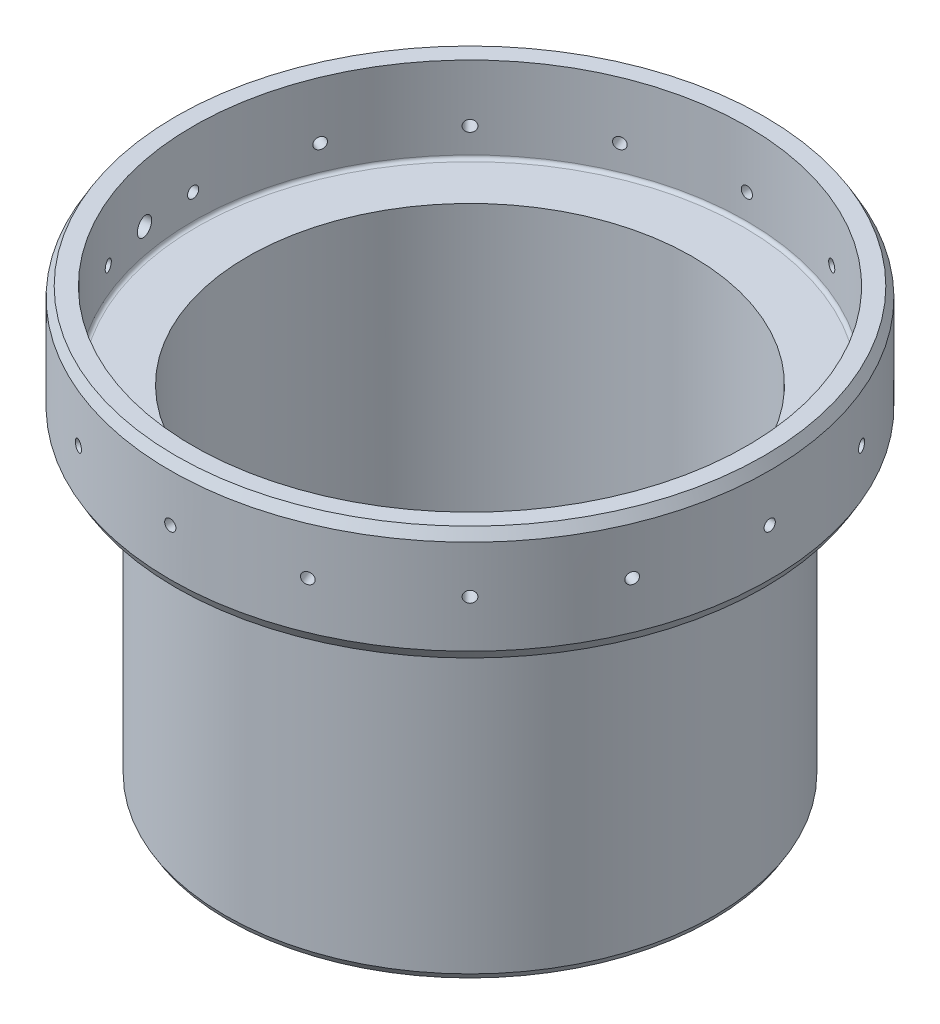
SolidWorks part; units mm, degrees
material "6061-T6 (SS)"
ref_plane "Front Plane" through (0, 0, 0) normal (0, 0, 1) x (1, 0, 0)
ref_plane "Top Plane" through (0, 0, 0) normal (0, 1, 0) x (1, 0, 0)
ref_plane "Right Plane" through (0, 0, 0) normal (1, 0, 0) x (0, 0, -1)
sketch "Sketch1" plane through (0, 0, 0) normal (0, 0, 1) x (1, 0, 0)
  line L0 (0, 0) -> (0, 9.1321) construction
  line L1 (0, 0) -> (-61.595, 0) construction
  line L2 (-61.595, 0) -> (-66.675, 0)
  line L3 (-66.675, 0) -> (-66.675, -25.4)
  line L4 (-66.675, -25.4) -> (-54.5465, -25.4)
  line L5 (-54.5465, -25.4) -> (-54.5465, -95.25)
  line L6 (-54.5465, -95.25) -> (-49.4665, -95.25)
  line L7 (-49.4665, -95.25) -> (-49.4665, -19.05)
  line L8 (-49.4665, -19.05) -> (-61.595, -19.05)
  line L9 (-61.595, -19.05) -> (-61.595, 0)
  dimension "D1" = 5.08
  dimension "D2" = 66.675
  dimension "D3" = 25.4
  dimension "D4" = 6.35
  dimension "D5" = 69.85
  dimension "D6" = 5.08
  dimension "D7" = 54.5465
revolve "Revolve6" add sketch "Sketch1" angle 360 about L0
sketch "Sketch2" plane through (0, 0, 0) normal (0, 1, 0) x (1, 0, 0)
  line L0 (0, 0) -> (-66.675, 0) construction
  line L1 (0, 0) -> (-65.3939, -13.0076) construction
  circle A0 centre (0, 0) radius 66.675 construction
  dimension "D1" = 11.25
ref_plane "Plane1" through (-66.675, 0, 0) normal (-1, 0, 0) x (0, 0, 1)
sketch "Sketch3" plane through (-66.675, 0, 0) normal (-1, 0, 0) x (0, 0, 1)
  line L0 (0, 0) -> (0, -12.7) construction
  dimension "D1" = 12.7
hole_wizard "Tap Drill for M3x0.5 Tap1" positions "Sketch5" profile "Sketch4" hole size "M3x0.5" standard "Ansi Metric"
sketch "Sketch5" plane through (-66.675, 0, 0) normal (-1, 0, 0) x (0, 0, 1)
  point P1 (0, -12.7)
sketch "Sketch4" plane through (-66.675, -12.7, 0) normal (0, 1, 0) x (0, 0, 1)
  line L0 (0, 0) -> (0, 10.9111)
  line L1 (0, 10.9111) -> (1.25, 10.16)
  line L2 (1.25, 10.16) -> (1.25, 0)
  line L5 (1.25, 0) -> (0, 0)
  line L10 (0, 10.9111) -> (-1.25, 10.16) construction
  line L11 (0, -6.35) -> (0, 107.95) construction
  dimension "Hole Dia." = 2.5
  dimension "Hole Depth" = 10.16
  dimension "Drill Angle" = 118
pattern_circular "CirPattern1" count 16 over 360 about axis through (0, 0, 0) along (0, -1, 0) of "Tap Drill for M3x0.5 Tap1"
ref_plane "Plane2" through (-65.3939, 0, 13.0076) normal (-0.9808, 0, 0.1951) x (0.1951, 0, 0.9808)
sketch "Sketch6" plane through (-65.3939, 0, 13.0076) normal (-0.9808, 0, 0.1951) x (0.1951, 0, 0.9808)
  line L0 (0, 0) -> (0, -12.7) construction
  dimension "D1" = 12.7
hole_wizard "Tap Drill for #10-32 Tap1" positions "Sketch8" profile "Sketch7" hole size "#10-32" standard "Ansi Inch"
sketch "Sketch8" plane through (-65.3939, 0, 13.0076) normal (-0.9808, 0, 0.1951) x (0.1951, 0, 0.9808)
  point P1 (0, -12.7)
sketch "Sketch7" plane through (-65.3939, -12.7, 13.0076) normal (0, 1, 0) x (0.1951, 0, 0.9808)
  line L0 (0, 0) -> (0, 11.3733)
  line L1 (0, 11.3733) -> (2.0193, 10.16)
  line L2 (2.0193, 10.16) -> (2.0193, 0)
  line L5 (2.0193, 0) -> (0, 0)
  line L10 (0, 11.3733) -> (-2.0193, 10.16) construction
  line L11 (0, -6.35) -> (0, 107.95) construction
  dimension "Hole Dia." = 4.0386
  dimension "Hole Depth" = 10.16
  dimension "Drill Angle" = 118
sketch "Sketch9" plane through (0, -95.25, 0) normal (0, -1, 0) x (1, 0, 0)
  line L0 (54.5465, 0) -> (49.4665, 0) construction
  circle A1 centre (0, 0) radius 54.5465 construction
  circle A2 centre (0, 0) radius 49.4665 construction
  point P9 (52.0065, 0)
hole_wizard "Tap Drill for #4-40 Tap1" positions "3DSketch1" profile "Sketch10" hole size "#4-40" standard "Ansi Inch"
sketch3d "3DSketch1"
  point P0 (52.0065, -95.25, 0)
sketch "Sketch10" plane through (52.0065, -95.25, 0) normal (1, 0, 0) x (0, 0, -1)
  line L0 (0, 0) -> (0, 18.4592)
  line L1 (0, 18.4592) -> (1.1303, 17.78)
  line L2 (1.1303, 17.78) -> (1.1303, 0)
  line L5 (1.1303, 0) -> (0, 0)
  line L10 (0, 18.4592) -> (-1.1303, 17.78) construction
  line L11 (0, -6.35) -> (0, 107.95) construction
  dimension "Hole Dia." = 2.2606
  dimension "Hole Depth" = 17.78
  dimension "Drill Angle" = 118
pattern_circular "CirPattern2" count 8 over 360 about axis through (0, 0, 0) along (0, -1, 0) of "Tap Drill for #4-40 Tap1"
chamfer "Chamfer2" distance 1.27 angle 60 2 edges at (0, -25.4, -66.675) (0, 0, -66.675) first distance on face at (0, -25.4, -54.5465) first distance on face at (0, 0, -66.675)
chamfer "Chamfer4" distance 0.762 angle 60 1 edges at (0, -95.25, -54.5465) first distance on face at (36.7741, -95.25, -37.9044)
chamfer "Chamfer5" distance 0.762 angle 60 1 edges at (0, -95.25, -49.4665) first distance on face at (0, -95.25, 53.7845)
fillet "Fillet1" radius 0.762 2 edges at (0, -25.4, -54.5465) (0, -19.05, -61.595)
